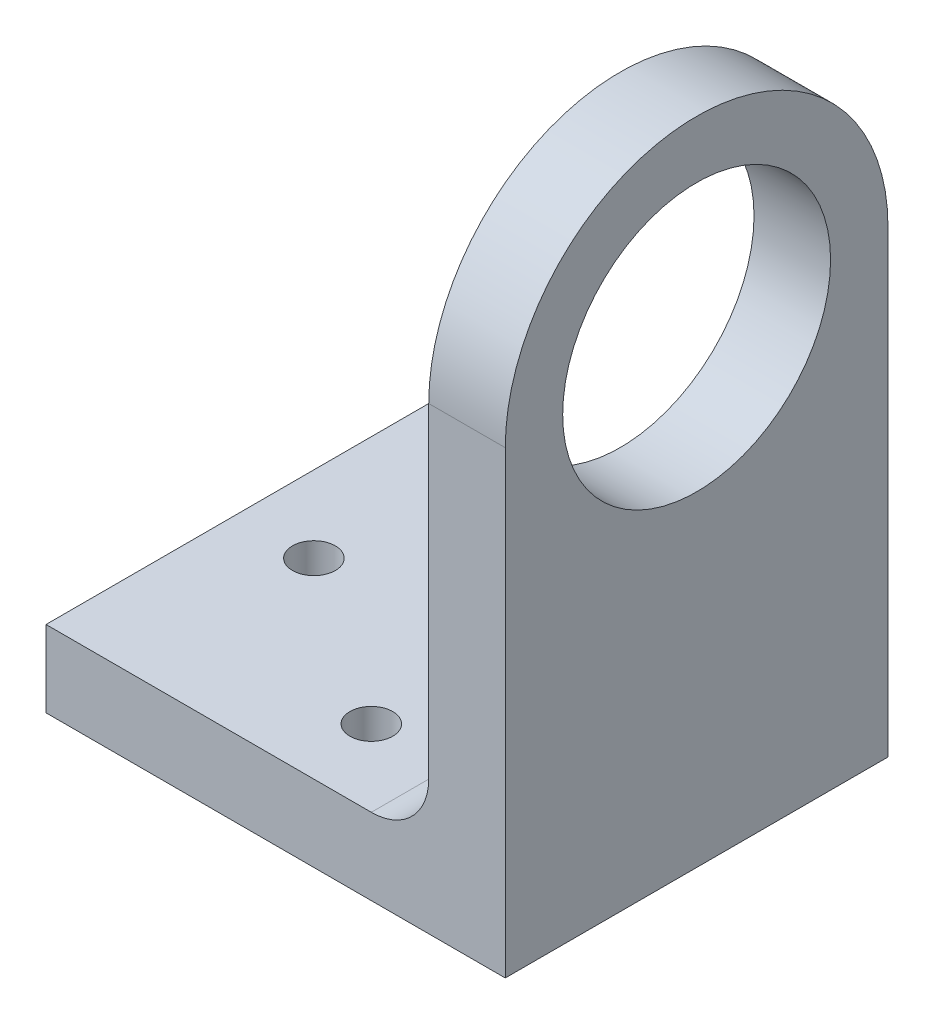
SolidWorks part; units mm, degrees
ref_plane "Front Plane" through (0, 0, 0) normal (0, 0, 1) x (1, 0, 0)
ref_plane "Top Plane" through (0, 0, 0) normal (0, 1, 0) x (1, 0, 0)
ref_plane "Right Plane" through (0, 0, 0) normal (1, 0, 0) x (0, 0, -1)
sketch "Sketch3" plane through (0, 0, 0) normal (1, 0, 0) x (0, 0, -1)
  line L1 (0, 0) -> (31.75, 0)
  line L2 (0, 0) -> (0, 31.75)
  line L4 (31.75, 0) -> (31.75, 31.75)
  circle A4 centre (15.875, 31.75) radius 11.1125
  arc A5 (0, 31.75) -> (31.75, 31.75) centre (15.875, 31.75) cw
  point P5 (0, 0)
  point P34 (15.875, 0)
  dimension "D4" = 22.225
  dimension "D1" = 31.75
  dimension "D2" = 31.75
extrude "Boss-Extrude1" add sketch "Sketch3" along normal blind 6.35
sketch "Sketch5" plane through (6.35, 0, 0) normal (1, 0, 0) x (0, 0, -1)
  line L1 (0, 0) -> (31.75, 0)
  line L2 (0, 0) -> (0, -6.35)
  line L3 (0, -6.35) -> (31.75, -6.35)
  line L4 (31.75, 0) -> (31.75, -6.35)
  dimension "D1" = 6.35
extrude "Boss-Extrude2" add sketch "Sketch5" against normal blind 38.1
fillet "Fillet1" radius 4.7625 1 edges at (0, 0, -15.875)
sketch "Sketch6" plane through (0, 0, 0) normal (0, 1, 0) x (1, 0, 0)
  line L0 (-31.75, 0) -> (-4.7625, 0) construction
  line L1 (-4.7625, 0) -> (-4.7625, 31.75) construction
  line L2 (-31.75, 31.75) -> (-31.75, 0) construction
  line L3 (0, 15.875) -> (-33.0413, 15.875) construction
  line L4 (0, 31.75) -> (0, 0) construction
  circle A0 centre (-11.1125, 6.35) radius 1.777
  circle A2 centre (-25.4, 15.875) radius 1.777
  circle A3 centre (-11.1125, 25.4) radius 1.777
  dimension "D1" = 3.554
  dimension "D2" = 6.35
  dimension "D3" = 6.35
  dimension "D4" = 6.35
extrude "Cut-Extrude1" cut sketch "Sketch6" against normal through all
equation "\"D1@Sketch6\" = 3.3mm + \"normTol\""
equation "\"tightTol\"= 0.005in"
equation "\"normTol\"= 0.01in"
equation "\"looseTol\"= 0.02in"
